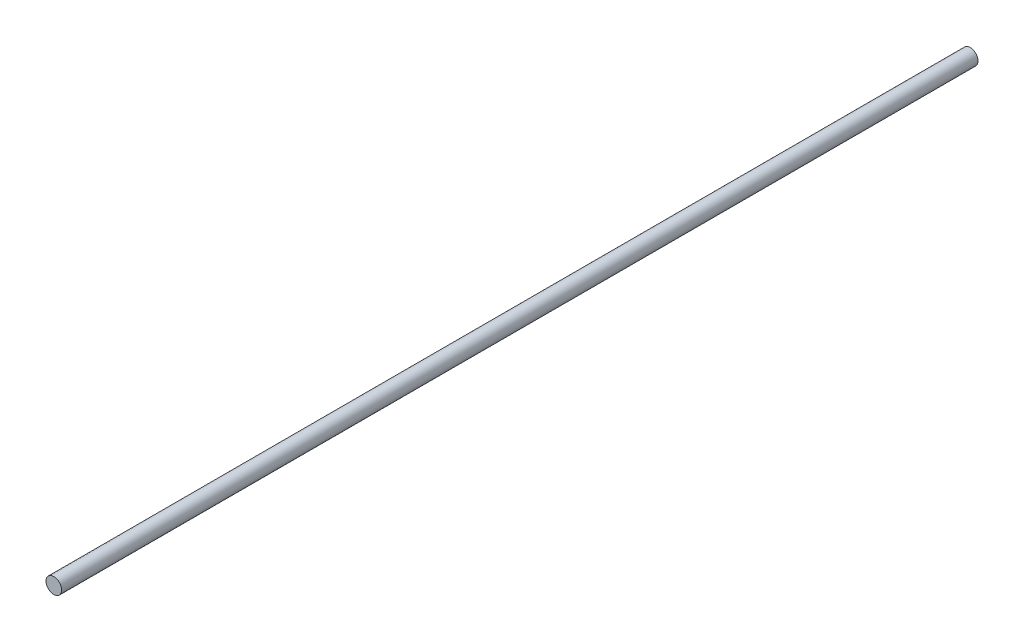
SolidWorks part; units mm, degrees
ref_plane "Front Plane" through (0, 0, 0) normal (0, 0, 1) x (1, 0, 0)
ref_plane "Top Plane" through (0, 0, 0) normal (0, 1, 0) x (1, 0, 0)
ref_plane "Right Plane" through (0, 0, 0) normal (1, 0, 0) x (0, 0, -1)
sketch "Sketch1" plane through (0, 0, 0) normal (0, 0, 1) x (1, 0, 0)
  line L5 (-1.4142, 1.4142) -> (1.4142, -1.4142) construction
  line L6 (-1.4142, -1.4142) -> (1.4142, 1.4142) construction
  circle A0 centre (0, 0) radius 2
  point P0 (0, 0)
  dimension "D3" = 4
extrude "Boss-Extrude1" add sketch "Sketch1" along normal mid plane 235
sketch "Sketch2" plane through (0, 0, 117.5) normal (0, 0, 1) x (1, 0, 0)
  circle A0 centre (0, 0) radius 4.7826
